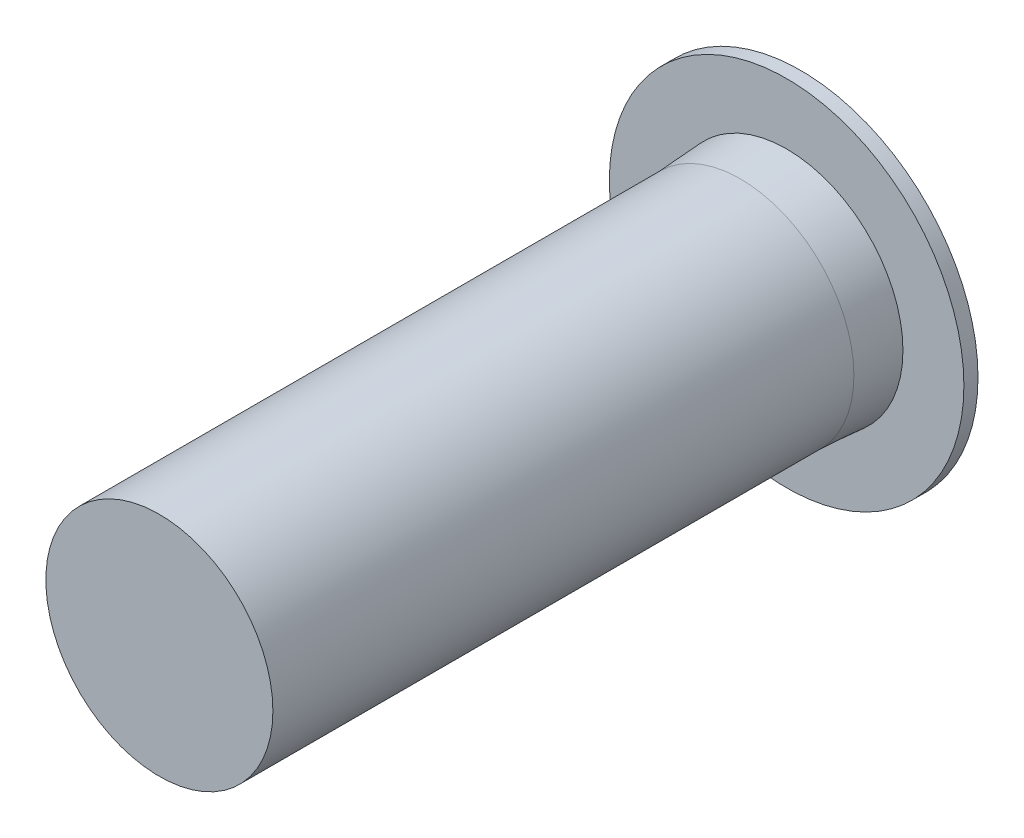
SolidWorks part; units mm, degrees
ref_plane "Front Plane" through (0, 0, 0) normal (0, 0, 1) x (1, 0, 0)
ref_plane "Top Plane" through (0, 0, 0) normal (0, 1, 0) x (1, 0, 0)
ref_plane "Right Plane" through (0, 0, 0) normal (1, 0, 0) x (0, 0, -1)
sketch "Sketch1" plane through (0, 0, 0) normal (0, 0, 1) x (1, 0, 0)
  circle A0 centre (0, 0) radius 5.61
  dimension "D1" = 11.22
ref_plane "Plane1" through (0, 0, 2.23) normal (0, 0, 1) x (1, 0, 0)
sketch "Sketch2" plane through (0, 0, 2.23) normal (0, 0, 1) x (1, 0, 0)
  circle A0 centre (0, 0) radius 5.475
  dimension "D1" = 10.95
ref_plane "Plane2" through (0, 0, 30.25) normal (0, 0, 1) x (1, 0, 0)
sketch "Sketch3" plane through (0, 0, 30.25) normal (0, 0, 1) x (1, 0, 0)
  circle A0 centre (0, 0) radius 5.475
  circle A1 centre (0, 0) radius 5.475 construction
loft "Loft1" add profiles "Sketch2", "Sketch1" connector at (-4.6212, -2.9361, 2.23) connector at (-4.7461, -2.9911, 0)
loft "Loft2" add profiles "Sketch3", "Sketch2<2>" connector at (-2.8046, 4.7021, 30.25) connector at (-2.6104, 4.8126, 2.23)
sketch "Sketch2<2>" plane through (0, 0, 2.23) normal (0, 0, 1) x (1, 0, 0) same geometry as "Sketch2"
sketch "Sketch4" plane through (0, 0, 0) normal (0, 0, -1) x (-1, 0, 0)
  circle A0 centre (0, 0) radius 8.55
  dimension "D1" = 17.1
extrude "Boss-Extrude1" add sketch "Sketch4" along normal blind 0.68
sketch "Sketch5" plane through (0, 0, -0.68) normal (0, 0, -1) x (-1, 0, 0)
  circle A0 centre (0, 0) radius 4.92
  dimension "D1" = 9.84
extrude "Cut-Extrude1" cut sketch "Sketch5" against normal blind 16.57
sketch "Sketch6" plane through (0, 0, 0) normal (0, 1, 0) x (1, 0, 0)
  line L0 (8.55, 0) -> (8.55, 0.68)
  line L1 (8.55, 0) -> (8.55, 0.68) construction
  line L2 (8.55, 0.68) -> (5.7093, 0.68)
  line L3 (8.55, 0.68) -> (-8.55, 0.68) construction
  line L4 (5.7093, 0.68) -> (5.6, 1.5703)
  line L5 (5.6, 1.5703) -> (5.6, 13.1751)
  line L6 (5.6, 13.1751) -> (4.92, 13.1751)
  line L7 (4.92, 13.1751) -> (4.92, 0)
  line L8 (-5.61, 0) -> (5.61, 0) construction
  line L9 (4.92, 0) -> (8.55, 0)
  line L12 (4.92, -15.89) -> (4.92, 0.68) construction
  dimension "D1" = 0.68
  dimension "D2" = 0.68
  dimension "D3" = 173
